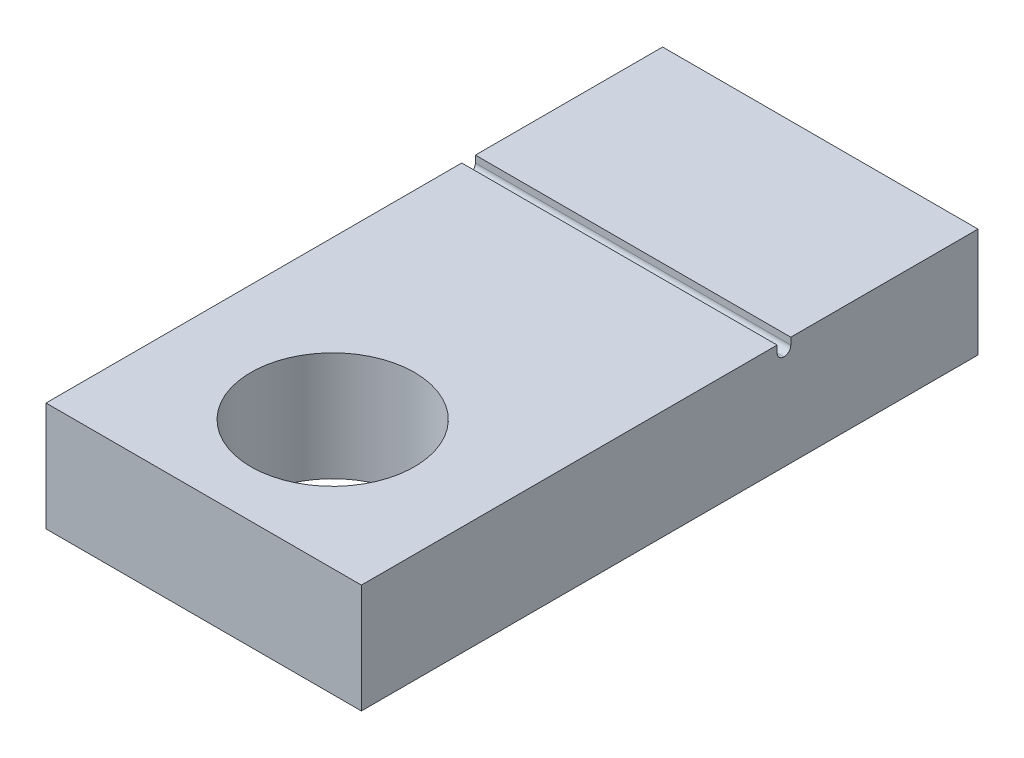
SolidWorks part; units mm, degrees
material "PUR"
ref_plane "Front Plane" through (0, 0, 0) normal (0, 0, 1) x (1, 0, 0)
ref_plane "Top Plane" through (0, 0, 0) normal (0, 1, 0) x (1, 0, 0)
ref_plane "Right Plane" through (0, 0, 0) normal (1, 0, 0) x (0, 0, -1)
sketch "Sketch1" plane through (0, 0, 0) normal (0, 1, 0) x (1, 0, 0)
  line L0 (11.5687, 17.4647) -> (11.5687, -17.4647)
  line L1 (-11.5687, 17.4647) -> (11.5687, 17.4647)
  line L2 (-11.5687, 17.4647) -> (-11.5687, -17.4647)
  line L3 (-11.5687, -17.4647) -> (11.5687, -17.4647)
  line L4 (0, 17.4647) -> (0, -17.4647) construction
  circle A0 centre (0, -8.0024) radius 1.5
  circle A1 centre (0, -8.0024) radius 6
extrude "Boss-Extrude1" add sketch "Sketch1" along normal blind 8 contours L1 L4 A1 L3 L0 | L4 L1 L2 L3 A1 region at (6.3112, 0, -1.3021) region at (-6.3112, 0, -1.3021)
sketch "Sketch2" plane through (0, 0, 0) normal (0, -1, 0) x (1, 0, 0)
  line L1 (-11.5687, -17.4647) -> (11.5687, -17.4647)
  line L2 (-11.5687, -17.4647) -> (-11.5687, -27.7714)
  line L3 (-11.5687, -27.7714) -> (11.5687, -27.7714)
  line L4 (11.5687, -17.4647) -> (11.5687, -27.7714)
extrude "Boss-Extrude2" add sketch "Sketch2" against normal blind 8
sketch "Sketch4" plane through (11.5687, 0, 0) normal (1, 0, 0) x (0, 0, -1)
  line L0 (27.7714, 8) -> (-17.4647, 8) construction
  line L1 (13.5362, -15.8896) -> (13.5362, 8) construction
  line L3 (14.0362, 9) -> (13.0362, 9)
  line L4 (14.0362, 9) -> (14.0362, 7)
  line L5 (14.0362, 7) -> (13.0362, 7)
  line L6 (13.0362, 9) -> (13.0362, 7)
  line L7 (14.0362, 9) -> (13.0362, 7) construction
  line L8 (14.0362, 7) -> (13.0362, 9) construction
  point P0 (13.5362, 8)
  dimension "D1" = 2
  dimension "D2" = 1
extrude "Cut-Extrude1" cut sketch "Sketch4" against normal blind 60
fillet "Fillet1" radius 0.5 2 edges at (0, 7, -14.0362) (0, 7, -13.0362)
